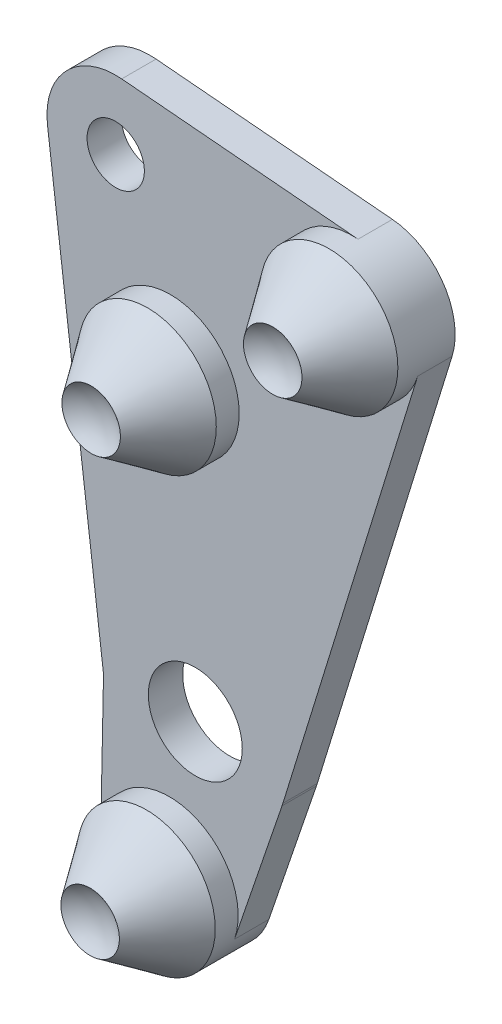
SolidWorks part; units mm, degrees
note: '?' marks a value the reader was unsure of. The reader was unsure of these and kept them because the rebuilt part matched: shared geometry of "Sketch1<4>", "Sketch2<4>".
ref_plane "Front Plane" through (0, 0, 0) normal (0, 0, 1) x (1, 0, 0)
ref_plane "Top Plane" through (0, 0, 0) normal (0, 1, 0) x (1, 0, 0)
ref_plane "Right Plane" through (0, 0, 0) normal (1, 0, 0) x (0, 0, -1)
sketch "Sketch1" plane through (0, 0, 0) normal (0, 0, 1) x (1, 0, 0)
  line L0 (0, 0) -> (-64.9837, 0) construction
  line L1 (0, 0) -> (-4.1676, 23.6354) construction
  line L2 (0, 0) -> (13.6808, 37.5877) construction
  line L3 (-10.1427, 23.0895) -> (-7.9668, -0.7278)
  line L4 (-7.8628, 28.3625) -> (9.9856, 42.3148)
  line L5 (19.4145, 35.8201) -> (7.6449, -2.3569)
  circle A0 centre (0, 0) radius 8
  arc A1 (-7.8628, 28.3625) -> (-10.1427, 23.0895) centre (-4.1676, 23.6354) ccw
  circle A2 centre (13.6808, 37.5877) radius 6
  circle A4 centre (13.6808, 37.5877) radius 4 construction
  circle A5 centre (-2.1676, 25.1988) radius 6
  circle A6 centre (-2.1676, 25.1988) radius 4 construction
  dimension "D1" = 16
  dimension "D4" = 12
  dimension "D7" = 12
  dimension "D8" = 12
  dimension "D9" = 8
  dimension "D10" = 2
  dimension "D11" = 8
  dimension "D2" = 24
  dimension "D3" = 80
  dimension "D5" = 40
  dimension "D6" = 110
sketch "Sketch2" plane through (0, 0, 0) normal (0, 0, 1) x (1, 0, 0)
  line L0 (0, 0) -> (-64.9837, 0) construction
  line L1 (-8.2562, -12.6821) -> (-7.9984, 0.1606)
  line L2 (0, 0) -> (-2.2574, -12.8025) construction
  line L3 (3.4208, -14.741) -> (7.5709, -2.5847)
  circle A0 centre (0, 0) radius 8
  circle A2 centre (-2.2574, -12.8025) radius 6
  circle A4 centre (-2.2574, -12.8025) radius 4 construction
  dimension "D5" = 80
  dimension "D6" = 12
  dimension "D7" = 8
  dimension "D4" = 13
extrude "Boss-Extrude1" add sketch "Sketch1" along normal blind 3 contours A2 L4 A1 L3 A0 L5 | A1 | A2 | A0 | A5
sketch "Sketch8" plane through (0, 0, 0) normal (0, 0, 1) x (1, 0, 0)
  line L0 (0, 0) -> (-64.9837, 0) construction
  line L1 (0, 0) -> (-6.9459, 39.3923) construction
  line L2 (-6.423, 45.3695) -> (14.2037, 43.5649)
  line L3 (-12.8995, 38.6472) -> (-7.9381, -0.9935)
  line L4 (14.2037, 43.5649) -> (0, 8)
  circle A0 centre (0, 0) radius 8
  circle A1 centre (-6.9459, 39.3923) radius 6
  circle A2 centre (-6.9459, 39.3923) radius 4 construction
  circle A3 centre (13.6808, 37.5877) radius 6 construction
  dimension "D1" = 40
  dimension "D3" = 12
  dimension "D4" = 8
  dimension "D2" = 80
extrude "Boss-Extrude5" add sketch "Sketch8" along normal blind 3 contours A1 L3 A0 L4 L2
extrude "Boss-Extrude2" add sketch "Sketch2" along normal blind 3
sketch "Sketch3" plane through (0, 0, 3) normal (0, 0, 1) x (1, 0, 0)
  circle A0 centre (0, 0) radius 4.1
  dimension "D1" = 8.2
extrude "Cut-Extrude1" cut sketch "Sketch3" against normal blind 50
ref_axis "Axis1" through (13.6808, 37.5877, 0) along (0, 0, 1)?
ref_axis "Axis2" through (-2.1676, 25.1988, 0) along (0, 0, 1)?
ref_axis "Axis3" through (-2.2574, -12.8025, 0) along (0, 0, 1)?
ref_axis "Axis4" through (0, 0, 0) along (0, 0, 1)?
extrude "Boss-Extrude3" add sketch "Sketch1<4>" along normal blind 10 contours A2 | A5
sketch "Sketch1<4>" plane through (0, 0, 0) normal (0, 0, 1) x (1, 0, 0) same geometry as "Sketch1"
extrude "Boss-Extrude4" add sketch "Sketch2<4>" along normal blind 10 contours A2
sketch "Sketch2<4>" plane through (0, 0, 0) normal (0, 0, 1) x (1, 0, 0) same geometry as "Sketch2"
ref_point "Point2"
ref_point "Point4"
ref_point "Point6"
ref_plane "Plane1" through (13.6808, 0, 0) normal (1, 0, 0) x (0, 0, -1)
ref_plane "Plane2" through (-2.1676, 0, 0) normal (1, 0, 0) x (0, 0, -1)
ref_plane "Plane3" through (-2.2574, 0, 0) normal (1, 0, 0) x (0, 0, -1)
sketch "Sketch5" plane through (13.6808, 0, 0) normal (1, 0, 0) x (0, 0, -1)
  line L0 (-10, 37.5877) -> (-13, 37.5877) construction
  line L1 (0, 37.5877) -> (-23.7634, 37.5877) construction
  line L2 (-13, 41.5877) -> (-13, 33.5877)
  circle A0 centre (-13, 37.5877) radius 4
  dimension "D2" = 8
  dimension "D1" = 3
sketch "Sketch6" plane through (-2.1676, 0, 0) normal (1, 0, 0) x (0, 0, -1)
  line L0 (-10, 25.1988) -> (-13, 25.1988) construction
  line L1 (0, 25.1988) -> (-23.7634, 25.1988) construction
  line L2 (-13, 29.1988) -> (-13, 21.1988)
  circle A0 centre (-13, 25.1988) radius 4
  dimension "D2" = 8
  dimension "D1" = 3
sketch "Sketch7" plane through (-2.2574, 0, 0) normal (1, 0, 0) x (0, 0, -1)
  line L0 (-10, -12.8025) -> (-13, -12.8025) construction
  line L1 (-13, -8.8025) -> (-13, -16.8025)
  circle A0 centre (-13, -12.8025) radius 4
  dimension "D2" = 8
  dimension "D1" = 3
revolve "Cut-Revolve1" cut sketch "Sketch5" angle 360 about L2
revolve "Cut-Revolve2" cut sketch "Sketch6" angle 360 about L2
revolve "Cut-Revolve3" cut sketch "Sketch7" angle 360 about L1
chamfer "Chamfer1" distance 5 angle 35 3 edges at (3.7426, -12.8025, 10) (19.6808, 37.5877, 10) (3.8324, 25.1988, 10)
sketch "Sketch9" plane through (0, 0, 0) normal (0, 0, -1) x (-1, 0, 0)
  circle A0 centre (6.9459, 39.3923) radius 2.5
extrude "Cut-Extrude2" cut sketch "Sketch9" against normal blind 3 contours A0
